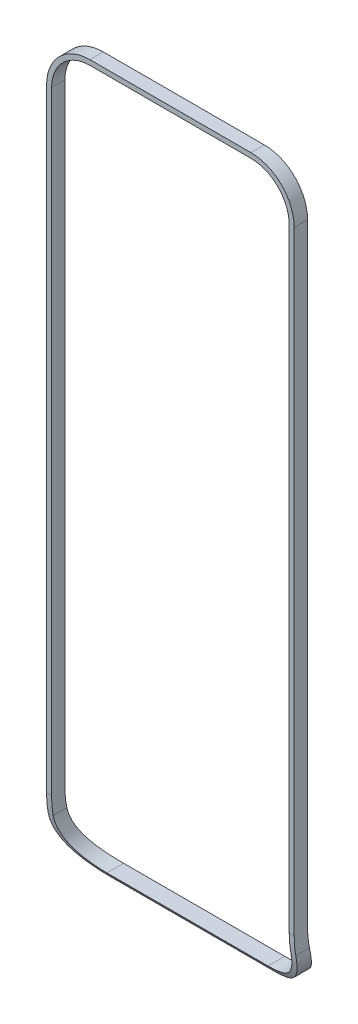
SolidWorks part; units mm, degrees
ref_plane "Front Plane" through (0, 0, 0) normal (0, 0, 1) x (1, 0, 0)
ref_plane "Top Plane" through (0, 0, 0) normal (0, 1, 0) x (1, 0, 0)
ref_plane "Right Plane" through (0, 0, 0) normal (1, 0, 0) x (0, 0, -1)
sketch "Sketch1" plane through (0, 0, 0) normal (0, 0, 1) x (1, 0, 0)
  line L0 (-13, 100) -> (-13, 1750)
  line L1 (100, 0) -> (521, 0)
  line L2 (0, 100) -> (0, 1750)
  line L3 (100, 1850) -> (521, 1850)
  line L4 (621, 100) -> (621, 1750)
  line L5 (100, 1863) -> (521, 1863)
  line L6 (634, 100) -> (634, 1750)
  line L7 (100, -13) -> (521, -13)
  arc A0 (100, 0) -> (0, 100) centre (100, 100) cw
  arc A1 (521, 0) -> (621, 100) centre (521, 100) ccw
  arc A2 (521, 1850) -> (621, 1750) centre (521, 1750) cw
  arc A3 (0, 1750) -> (100, 1850) centre (100, 1750) cw
  arc A4 (-13, 1750) -> (100, 1863) centre (100, 1750) cw
  arc A5 (521, 1863) -> (634, 1750) centre (521, 1750) cw
  arc A6 (521, -13) -> (634, 100) centre (521, 100) ccw
  arc A7 (100, -13) -> (-13, 100) centre (100, 100) cw
  point P8 (0, 0)
  point P11 (621, 0)
  point P14 (621, 1850)
  dimension "D3" = 100
  dimension "D1" = 1850
  dimension "D2" = 621
  dimension "D4" = 13
extrude "Boss-Extrude1" add sketch "Sketch1" against normal blind 100
sketch "Sketch2" plane through (0, 0, 0) normal (1, 0, 0) x (0, 0, -1)
  line L2 (35, 1863) -> (35, 147.1206)
  line L3 (100, -13) -> (53.9166, -13)
  line L7 (0, 147.1206) -> (0, -13)
  line L8 (0, -13) -> (53.9166, -13)
  line L9 (100, -13) -> (100, 1863)
  line L10 (100, 1863) -> (35, 1863)
  line L11 (100, 1863) -> (0, 1863) construction
  line L12 (100, 1750) -> (100, 1863) construction
  arc A0 (35, 147.1206) -> (100, -13) centre (264.72, 147.1206) ccw
  arc A1 (53.9166, -13) -> (0, 147.1206) centre (264.72, 147.1206) cw
  point P0 (3.1984, -7.5045)
  line M8 (0, 100) -> (100, 100)
  line M10 (100, 1750) -> (0, 1750)
  dimension "D2" = 264.72
  dimension "D1" = 35
extrude "Cut-Extrude1" cut sketch "Sketch2" along normal through all and the other way through all contours L8 A1 L7 M8 | A0 L9 M8 | L2 A0 M8 M10 | L9 L10 L2 A0 | A1 L7 L8 region at (0, 925.5797, -67.5221) region at (0, 58.4997, -77.4917) region at (0, 24.0575, -16.207)
